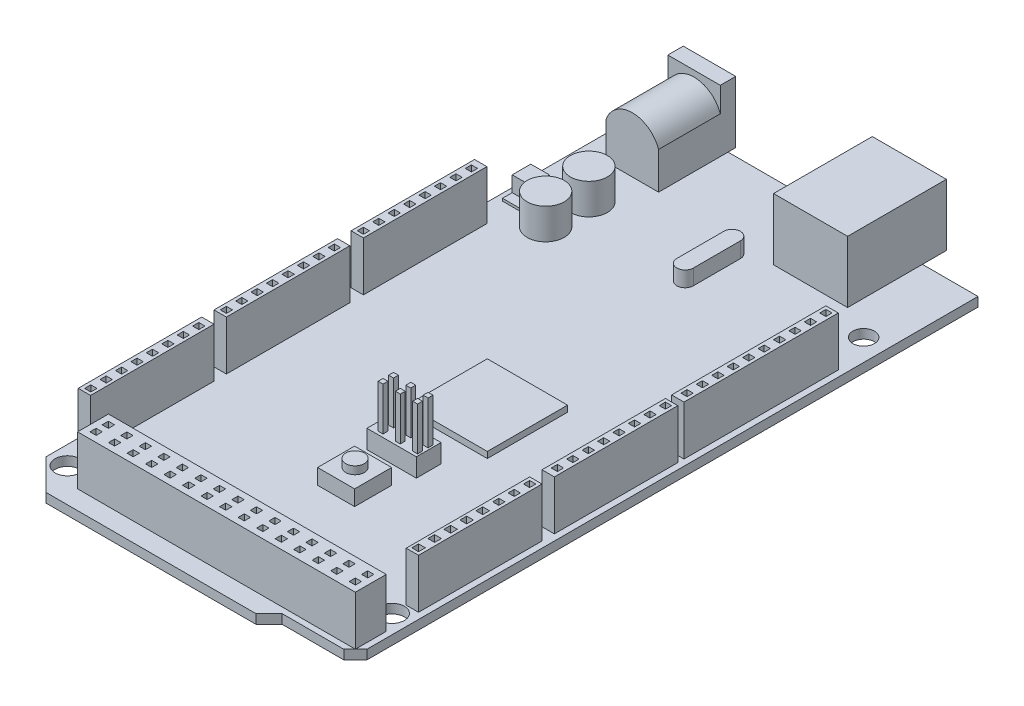
SolidWorks part; units mm, degrees
ref_plane "Front Plane" through (0, 0, 0) normal (0, 0, 1) x (1, 0, 0)
ref_plane "Top Plane" through (0, 0, 0) normal (0, 1, 0) x (1, 0, 0)
ref_plane "Right Plane" through (0, 0, 0) normal (1, 0, 0) x (0, 0, -1)
sketch "Sketch1" plane through (0, 0, 0) normal (0, 1, 0) x (1, 0, 0)
  line L0 (0, 0) -> (34, 0)
  line L1 (34, 0) -> (36.1213, 2.1213)
  line L2 (36.1213, 2.1213) -> (46.1213, 2.1213)
  line L3 (46.1213, 2.1213) -> (48, 4)
  line L4 (48, 4) -> (48, 103)
  line L5 (48, 103) -> (-5, 103)
  line L6 (-5, 103) -> (-5, 5)
  line L7 (-5, 5) -> (0, 0)
  dimension "D1" = 34
  dimension "D2" = 45
  dimension "D3" = 10
  dimension "D4" = 45
  dimension "D5" = 99
  dimension "D6" = 53
  dimension "D7" = 98
  dimension "D8" = 45
extrude "Boss-Extrude3" add sketch "Sketch1" along normal blind 1.5
sketch "Sketch4" plane through (0, 1.5, 0) normal (0, 1, 0) x (1, 0, 0)
  line L0 (46.1213, 2.1213) -> (48, 4) construction
  line L1 (47.0607, 3.0607) -> (2.0607, 3.0607)
  line L2 (47.0607, 3.0607) -> (47.0607, 8.0607)
  line L3 (47.0607, 8.0607) -> (2.0607, 8.0607)
  line L4 (2.0607, 3.0607) -> (2.0607, 8.0607)
  dimension "D1" = 45
  dimension "D2" = 5
extrude "Boss-Extrude5" add sketch "Sketch4" along normal blind 8
sketch "Sketch7" plane through (0, 9.5, 0) normal (0, 1, 0) x (1, 0, 0)
  line L0 (47.0607, 3.0607) -> (47.0607, 8.0607) construction
  line L1 (45.0607, 7.0607) -> (46.0607, 7.0607)
  line L2 (45.0607, 7.0607) -> (45.0607, 6.0607)
  line L3 (45.0607, 6.0607) -> (46.0607, 6.0607)
  line L4 (46.0607, 7.0607) -> (46.0607, 6.0607)
  line L5 (45.0607, 5.0607) -> (46.0607, 5.0607)
  line L6 (45.0607, 5.0607) -> (45.0607, 4.0607)
  line L7 (45.0607, 4.0607) -> (46.0607, 4.0607)
  line L8 (46.0607, 5.0607) -> (46.0607, 4.0607)
  line L9 (43.0607, 4.0607) -> (42.0607, 4.0607)
  line L10 (43.0607, 4.0607) -> (43.0607, 5.0607)
  line L11 (43.0607, 5.0607) -> (42.0607, 5.0607)
  line L12 (42.0607, 4.0607) -> (42.0607, 5.0607)
  line L13 (43.0607, 6.0407) -> (42.0607, 6.0407)
  line L14 (43.0607, 6.0407) -> (43.0607, 7.0407)
  line L15 (43.0607, 7.0407) -> (42.0607, 7.0407)
  line L16 (42.0607, 6.0407) -> (42.0607, 7.0407)
  line L17 (40.0607, 7.0407) -> (39.0607, 7.0407)
  line L18 (40.0607, 7.0407) -> (40.0607, 6.0407)
  line L19 (40.0607, 6.0407) -> (39.0607, 6.0407)
  line L20 (39.0607, 7.0407) -> (39.0607, 6.0407)
  line L21 (39.0607, 5.0607) -> (40.0607, 5.0607)
  line L22 (39.0607, 5.0607) -> (39.0607, 4.0607)
  line L23 (39.0607, 4.0607) -> (40.0607, 4.0607)
  line L24 (40.0607, 5.0607) -> (40.0607, 4.0607)
  line L25 (37.0607, 4.0607) -> (36.0607, 4.0607)
  line L26 (37.0607, 4.0607) -> (37.0607, 5.0607)
  line L27 (37.0607, 5.0607) -> (36.0607, 5.0607)
  line L28 (36.0607, 4.0607) -> (36.0607, 5.0607)
  line L29 (36.0607, 6.0407) -> (37.0607, 6.0407)
  line L30 (36.0607, 6.0407) -> (36.0607, 7.0407)
  line L31 (36.0607, 7.0407) -> (37.0607, 7.0407)
  line L32 (37.0607, 6.0407) -> (37.0607, 7.0407)
  line L33 (34.0607, 7.0407) -> (33.0607, 7.0407)
  line L34 (34.0607, 7.0407) -> (34.0607, 6.0407)
  line L35 (34.0607, 6.0407) -> (33.0607, 6.0407)
  line L36 (33.0607, 7.0407) -> (33.0607, 6.0407)
  line L37 (33.0607, 5.0607) -> (34.0607, 5.0607)
  line L38 (33.0607, 5.0607) -> (33.0607, 4.0607)
  line L39 (33.0607, 4.0607) -> (34.0607, 4.0607)
  line L40 (34.0607, 5.0607) -> (34.0607, 4.0607)
  line L41 (31.0607, 4.0607) -> (30.0607, 4.0607)
  line L42 (31.0607, 4.0607) -> (31.0607, 5.0607)
  line L43 (31.0607, 5.0607) -> (30.0607, 5.0607)
  line L44 (30.0607, 4.0607) -> (30.0607, 5.0607)
  line L45 (30.0607, 6.0407) -> (31.0607, 6.0407)
  line L46 (30.0607, 6.0407) -> (30.0607, 7.0407)
  line L47 (30.0607, 7.0407) -> (31.0607, 7.0407)
  line L48 (31.0607, 6.0407) -> (31.0607, 7.0407)
  line L49 (28.0607, 7.0407) -> (27.0607, 7.0407)
  line L50 (28.0607, 7.0407) -> (28.0607, 6.0407)
  line L51 (28.0607, 6.0407) -> (27.0607, 6.0407)
  line L52 (27.0607, 7.0407) -> (27.0607, 6.0407)
  line L57 (28.0607, 4.0607) -> (27.0607, 4.0607)
  line L58 (28.0607, 4.0607) -> (28.0607, 5.0607)
  line L59 (28.0607, 5.0607) -> (27.0607, 5.0607)
  line L60 (27.0607, 4.0607) -> (27.0607, 5.0607)
  line L61 (25.0607, 6.0407) -> (24.0607, 6.0407)
  line L62 (25.0607, 6.0407) -> (25.0607, 7.0407)
  line L63 (25.0607, 7.0407) -> (24.0607, 7.0407)
  line L64 (24.0607, 6.0407) -> (24.0607, 7.0407)
  line L65 (22.0607, 6.0407) -> (21.0607, 6.0407)
  line L66 (22.0607, 6.0407) -> (22.0607, 7.0407)
  line L67 (22.0607, 7.0407) -> (21.0607, 7.0407)
  line L68 (21.0607, 6.0407) -> (21.0607, 7.0407)
  line L69 (24.0607, 5.0607) -> (25.0607, 5.0607)
  line L70 (24.0607, 5.0607) -> (24.0607, 4.0607)
  line L71 (24.0607, 4.0607) -> (25.0607, 4.0607)
  line L72 (25.0607, 5.0607) -> (25.0607, 4.0607)
  line L77 (18.0607, 6.0407) -> (19.0607, 6.0407)
  line L78 (18.0607, 6.0407) -> (18.0607, 7.0407)
  line L79 (18.0607, 7.0407) -> (19.0607, 7.0407)
  line L80 (19.0607, 6.0407) -> (19.0607, 7.0407)
  line L81 (16.0607, 7.0407) -> (15.0607, 7.0407)
  line L82 (16.0607, 7.0407) -> (16.0607, 6.0407)
  line L83 (16.0607, 6.0407) -> (15.0607, 6.0407)
  line L84 (15.0607, 7.0407) -> (15.0607, 6.0407)
  line L85 (21.0607, 5.0607) -> (22.0607, 5.0607)
  line L86 (21.0607, 5.0607) -> (21.0607, 4.0607)
  line L87 (21.0607, 4.0607) -> (22.0607, 4.0607)
  line L88 (22.0607, 5.0607) -> (22.0607, 4.0607)
  line L89 (19.0607, 4.0607) -> (18.0607, 4.0607)
  line L90 (19.0607, 4.0607) -> (19.0607, 5.0607)
  line L91 (19.0607, 5.0607) -> (18.0607, 5.0607)
  line L92 (18.0607, 4.0607) -> (18.0607, 5.0607)
  line L93 (13.0607, 7.0407) -> (12.0607, 7.0407)
  line L94 (13.0607, 7.0407) -> (13.0607, 6.0407)
  line L95 (13.0607, 6.0407) -> (12.0607, 6.0407)
  line L96 (12.0607, 7.0407) -> (12.0607, 6.0407)
  line L97 (10.0607, 6.0407) -> (9.0607, 6.0407)
  line L98 (10.0607, 6.0407) -> (10.0607, 7.0407)
  line L99 (10.0607, 7.0407) -> (9.0607, 7.0407)
  line L100 (9.0607, 6.0407) -> (9.0607, 7.0407)
  line L105 (16.0607, 4.0607) -> (15.0607, 4.0607)
  line L106 (16.0607, 4.0607) -> (16.0607, 5.0607)
  line L107 (16.0607, 5.0607) -> (15.0607, 5.0607)
  line L108 (15.0607, 4.0607) -> (15.0607, 5.0607)
  line L109 (2.0607, 3.0607) -> (47.0607, 3.0607) construction
  line L110 (7.0607, 7.0407) -> (6.0607, 7.0407)
  line L111 (7.0607, 7.0407) -> (7.0607, 6.0407)
  line L112 (7.0607, 6.0407) -> (6.0607, 6.0407)
  line L113 (6.0607, 7.0407) -> (6.0607, 6.0407)
  line L114 (4.0607, 7.0407) -> (3.0607, 7.0407)
  line L115 (4.0607, 7.0407) -> (4.0607, 6.0407)
  line L116 (4.0607, 6.0407) -> (3.0607, 6.0407)
  line L121 (13.0607, 4.0607) -> (12.0607, 4.0607)
  line L122 (13.0607, 4.0607) -> (13.0607, 5.0607)
  line L123 (13.0607, 5.0607) -> (12.0607, 5.0607)
  line L124 (12.0607, 4.0607) -> (12.0607, 5.0607)
  line L125 (3.0607, 7.0407) -> (3.0607, 6.0407)
  line L137 (10.0607, 4.0607) -> (9.0607, 4.0607)
  line L138 (10.0607, 4.0607) -> (10.0607, 5.0607)
  line L139 (10.0607, 5.0607) -> (9.0607, 5.0607)
  line L140 (9.0607, 4.0607) -> (9.0607, 5.0607)
  line L153 (7.0607, 4.0607) -> (6.0607, 4.0607)
  line L154 (7.0607, 4.0607) -> (7.0607, 5.0607)
  line L155 (7.0607, 5.0607) -> (6.0607, 5.0607)
  line L156 (6.0607, 4.0607) -> (6.0607, 5.0607)
  line L169 (4.0607, 4.0607) -> (3.0607, 4.0607)
  line L170 (4.0607, 4.0607) -> (4.0607, 5.0607)
  line L171 (4.0607, 5.0607) -> (3.0607, 5.0607)
  line L172 (3.0607, 4.0607) -> (3.0607, 5.0607)
  line L182 (47.0607, 8.0607) -> (2.0607, 8.0607) construction
  dimension "D1" = 1
  dimension "D2" = 1
  dimension "D3" = 1
  dimension "D4" = 1
  dimension "D5" = 1
  dimension "D6" = 1
  dimension "D7" = 2
  dimension "D8" = 2
  dimension "D9" = 2
  dimension "D10" = 2
  dimension "D11" = 2
  dimension "D12" = 2
  dimension "D13" = 2
  dimension "D14" = 2
  dimension "D15" = 2
  dimension "D16" = 2
  dimension "D17" = 2
  dimension "D18" = 2
  dimension "D19" = 2
  dimension "D20" = 1
  dimension "D21" = 2
  dimension "D22" = 2
  dimension "D23" = 1
  dimension "D24" = 1
  dimension "D25" = 2
  dimension "D26" = 1
  dimension "D27" = 1
  dimension "D28" = 1
  dimension "D29" = 1
  dimension "D30" = 2
  dimension "D31" = 1
  dimension "D32" = 1
  dimension "D33" = 2
  dimension "D34" = 1
  dimension "D35" = 1
  dimension "D36" = 2
  dimension "D37" = 1
  dimension "D39" = 1
  dimension "D41" = 1
  dimension "D43" = 1
  dimension "D45" = 1
  dimension "D46" = 2
  dimension "D47" = 2
  dimension "D48" = 2
  dimension "D49" = 2
  dimension "D50" = 2
  dimension "D51" = 2
  dimension "D52" = 2
  dimension "D53" = 2
  dimension "D54" = 2
extrude "Cut-Extrude1" cut sketch "Sketch7" against normal up to surface (8 mm away) up to face at (26.7343, 1.5, -18.8112)
sketch "Sketch8" plane through (0, 1.5, 0) normal (0, 1, 0) x (1, 0, 0)
  line L0 (48, 4) -> (48, 103) construction
  line L1 (21, 29) -> (27, 29)
  line L2 (21, 29) -> (21, 23)
  line L3 (21, 23) -> (27, 23)
  line L4 (27, 29) -> (27, 23)
  line L5 (0, 0) -> (34, 0) construction
  dimension "D1" = 21
  dimension "D2" = 23
  dimension "D3" = 6
  dimension "D4" = 6
extrude "Boss-Extrude7" add sketch "Sketch8" along normal blind 2.5
sketch "Sketch10" plane through (0, 4, 0) normal (0, 1, 0) x (1, 0, 0)
  line L0 (21, 29) -> (21, 23) construction
  circle A0 centre (24, 26.0733) radius 1.5
  dimension "D1" = 3
  dimension "D2" = 3
extrude "Boss-Extrude8" add sketch "Sketch10" along normal blind 1.25
sketch "Sketch11" plane through (0, 1.5, 0) normal (0, 1, 0) x (1, 0, 0)
  line L0 (27, 29) -> (21, 29) construction
  line L1 (20, 36) -> (28, 36)
  line L2 (20, 36) -> (20, 32)
  line L3 (20, 32) -> (28, 32)
  line L4 (28, 36) -> (28, 32)
  line L5 (48, 4) -> (48, 103) construction
  dimension "D1" = 3
  dimension "D2" = 8
  dimension "D3" = 4
  dimension "D4" = 20
extrude "Boss-Extrude9" add sketch "Sketch11" along normal blind 3
sketch "Sketch12" plane through (0, 4.5, 0) normal (0, 1, 0) x (1, 0, 0)
  line L0 (28, 32) -> (28, 36) construction
  line L1 (26.9, 35) -> (27.7, 35)
  line L2 (26.9, 35) -> (26.9, 34.2)
  line L3 (26.9, 34.2) -> (27.7, 34.2)
  line L4 (27.7, 35) -> (27.7, 34.2)
  line L5 (24.9, 34.2) -> (24.1, 34.2)
  line L6 (24.9, 34.2) -> (24.9, 35)
  line L7 (24.9, 35) -> (24.1, 35)
  line L8 (24.1, 34.2) -> (24.1, 35)
  line L9 (21.3, 35) -> (22.1, 35)
  line L10 (21.3, 35) -> (21.3, 34.2)
  line L11 (21.3, 34.2) -> (22.1, 34.2)
  line L12 (22.1, 35) -> (22.1, 34.2)
  line L13 (21.3, 33.3) -> (22.1, 33.3)
  line L14 (21.3, 33.3) -> (21.3, 32.5)
  line L15 (21.3, 32.5) -> (22.1, 32.5)
  line L16 (22.1, 33.3) -> (22.1, 32.5)
  line L17 (24.1, 33.3) -> (24.9, 33.3)
  line L18 (24.1, 33.3) -> (24.1, 32.5)
  line L19 (24.1, 32.5) -> (24.9, 32.5)
  line L20 (24.9, 33.3) -> (24.9, 32.5)
  line L21 (26.9, 33.3) -> (27.7, 33.3)
  line L22 (26.9, 33.3) -> (26.9, 32.5)
  line L23 (26.9, 32.5) -> (27.7, 32.5)
  line L24 (27.7, 33.3) -> (27.7, 32.5)
  line L25 (28, 32) -> (28, 36) construction
  line L26 (28, 36) -> (20, 36) construction
  line L27 (20, 32) -> (28, 32) construction
  dimension "D1" = 0.8
  dimension "D2" = 0.3
  dimension "D3" = 0.3
  dimension "D4" = 1
  dimension "D5" = 0.5
  dimension "D6" = 2
  dimension "D7" = 2
  dimension "D8" = 2
  dimension "D9" = 2
extrude "Boss-Extrude10" add sketch "Sketch12" along normal blind 7
sketch "Sketch13" plane through (0, 1.5, 0) normal (0, 1, 0) x (1, 0, 0)
  line L0 (28, 36) -> (20, 36) construction
  line L1 (18, 53.5) -> (31, 53.5)
  line L2 (18, 53.5) -> (18, 40.5)
  line L3 (18, 40.5) -> (31, 40.5)
  line L4 (31, 53.5) -> (31, 40.5)
  line L5 (48, 4) -> (48, 103) construction
  dimension "D1" = 4.5
  dimension "D2" = 17
  dimension "D3" = 13
  dimension "D4" = 13
extrude "Boss-Extrude11" add sketch "Sketch13" along normal blind 1
sketch "Sketch14" plane through (0, 1.5, 0) normal (0, 1, 0) x (1, 0, 0)
  line L0 (48, 4) -> (48, 103) construction
  line L1 (27, 90.8728) -> (39, 90.8728)
  line L2 (27, 90.8728) -> (27, 106.8728)
  line L3 (27, 106.8728) -> (39, 106.8728)
  line L4 (39, 90.8728) -> (39, 106.8728)
  dimension "D1" = 9
  dimension "D2" = 12
  dimension "D3" = 16
extrude "Boss-Extrude12" add sketch "Sketch14" along normal blind 10
sketch "Sketch15" plane through (0, 0, -106.8728) normal (0, 0, -1) x (-1, 0, 0)
  line L0 (-37.5042, 2.8745) -> (-37.5042, 7.7767)
  line L1 (-37.5042, 7.7767) -> (-35.7809, 9.5)
  line L2 (-47.0607, 9.5) -> (-2.0607, 9.5) construction
  line L3 (-35.7809, 9.5) -> (-30.2715, 9.5)
  line L4 (-30.2715, 9.5) -> (-28.5482, 7.7767)
  line L5 (-28.5482, 7.7767) -> (-28.5482, 2.8745)
  line L6 (-28.5482, 2.8745) -> (-37.5042, 2.8745)
extrude "Cut-Extrude2" cut sketch "Sketch15" against normal blind 13
sketch "Sketch16" plane through (0, 0, -93.8728) normal (0, 0, -1) x (-1, 0, 0)
  line L0 (-37.5042, 7.7767) -> (-37.5042, 2.8745) construction
  line L1 (-35.8042, 7.78) -> (-30.2482, 7.78)
  line L2 (-35.8042, 7.78) -> (-35.8042, 4.3976)
  line L3 (-35.8042, 4.3976) -> (-30.2482, 4.3976)
  line L4 (-30.2482, 7.78) -> (-30.2482, 4.3976)
  line L5 (-28.5482, 2.8745) -> (-28.5482, 7.7767) construction
  dimension "D1" = 1.7
  dimension "D2" = 1.7
extrude "Boss-Extrude13" add sketch "Sketch16" along normal up to surface (13 mm away) up to face at (33.0262, 6.7171, -106.8728)
sketch "Sketch17" plane through (0, 0, -103) normal (0, 0, -1) x (-1, 0, 0)
  line L0 (-27, 1.5) -> (5, 1.5) construction
  line L1 (1, 1.5) -> (-7.5, 1.5)
  line L2 (1, 1.5) -> (1, 11.5)
  line L3 (1, 11.5) -> (-7.5, 11.5)
  line L4 (-7.5, 1.5) -> (-7.5, 11.5)
  dimension "D1" = 4
  dimension "D2" = 10
  dimension "D3" = 8.5
extrude "Boss-Extrude14" add sketch "Sketch17" along normal mid plane 2.5
sketch "Sketch18" plane through (0, 0, -101.75) normal (0, 0, 1) x (1, 0, 0)
  line L0 (-1, 7.5) -> (-1, 1.5)
  line L1 (-1, 1.5) -> (-1, 11.5) construction
  line L2 (-1, 1.5) -> (7.5, 1.5)
  line L3 (7.5, 1.5) -> (-1, 1.5) construction
  line L4 (7.5, 1.5) -> (7.5, 7.5)
  line L5 (7.5, 11.5) -> (7.5, 1.5) construction
  arc A0 (-1, 7.5) -> (7.5, 7.5) centre (3.25, 6.021) cw
  dimension "D3" = 4.5
  dimension "D1" = 6
  dimension "D2" = 6
extrude "Boss-Extrude15" add sketch "Sketch18" along normal blind 10
sketch "Sketch19" plane through (0, 0, -104.25) normal (0, 0, -1) x (-1, 0, 0)
  line L0 (1, 1.5) -> (1, 11.5) construction
  line L1 (1, 11.5) -> (-7.5, 11.5) construction
  circle A0 centre (-3, 6.5) radius 3
  dimension "D1" = 6
  dimension "D2" = 4
  dimension "D3" = 5
extrude "Cut-Extrude6" cut sketch "Sketch19" against normal blind 10
sketch "Sketch20" plane through (0, 0, -94.25) normal (0, 0, -1) x (-1, 0, 0)
  circle A0 centre (-3, 6.5) radius 0.5
  circle A1 centre (-3, 6.5) radius 3 construction
  dimension "D1" = 1
  dimension "D2" = 0
extrude "Boss-Extrude16" add sketch "Sketch20" along normal blind 8
dome "Dome1" faces to dome 1 distance 1 reverse direction no elliptical dome no face at (2.5, 6.5, -102.25) parameters "D1"=1
sketch "Sketch21" plane through (0, 1.5, 0) normal (0, 1, 0) x (1, 0, 0)
  line L0 (-1, 91.75) -> (7.5, 91.75) construction
  circle A0 centre (3.2048, 84.75) radius 3
  circle A1 centre (3.2048, 77.75) radius 3
  point P7 (3.25, 91.75)
  dimension "D1" = 6
  dimension "D2" = 6
  dimension "D3" = 7
  dimension "D4" = 7
extrude "Boss-Extrude17" add sketch "Sketch21" along normal blind 5
sketch "Sketch23" plane through (0, 1.5, 0) normal (0, 1, 0) x (1, 0, 0)
  line L1 (-3.8978, 84.0356) -> (-0.8721, 84.0356)
  line L2 (-3.8978, 84.0356) -> (-3.8978, 77.8497)
  line L3 (-3.8978, 77.8497) -> (-0.8721, 77.8497)
  line L4 (-0.8721, 84.0356) -> (-0.8721, 77.8497)
extrude "Boss-Extrude18" add sketch "Sketch23" along normal blind 0.4
sketch "Sketch24" plane through (0, 1.9, 0) normal (0, 1, 0) x (1, 0, 0)
  line L0 (-3.8978, 84.0356) -> (-3.8978, 77.8497) construction
  line L1 (-3.8978, 82.4355) -> (-0.8721, 82.4355)
  line L2 (-3.8978, 82.4355) -> (-3.8978, 79.4247)
  line L3 (-3.8978, 79.4247) -> (-0.8721, 79.4247)
  line L4 (-0.8721, 82.4355) -> (-0.8721, 79.4247)
  line L5 (-0.8721, 77.8497) -> (-0.8721, 84.0356) construction
extrude "Boss-Extrude19" add sketch "Sketch24" along normal blind 2.5
sketch "Sketch25" plane through (0, 1.5, 0) normal (0, 1, 0) x (1, 0, 0)
  line L0 (20.7718, 89.0501) -> (20.7718, 81.4302)
  line L2 (23.4528, 81.4302) -> (23.4528, 89.0501)
  arc A0 (20.7718, 89.0501) -> (23.4528, 89.0501) centre (22.1123, 89.0501) cw
  arc A1 (20.7718, 81.4302) -> (23.4528, 81.4302) centre (22.1123, 81.4302) ccw
extrude "Boss-Extrude20" add sketch "Sketch25" along normal blind 2.5
sketch "Sketch26" plane through (0, 1.5, 0) normal (0, 1, 0) x (1, 0, 0)
  line L0 (-5, 103) -> (-5, 5) construction
  line L1 (-1, 103) -> (-5, 103) construction
  circle A0 centre (-2, 89) radius 2
  dimension "D1" = 4
  dimension "D2" = 3
  dimension "D3" = 14
extrude "Cut-Extrude7" cut sketch "Sketch26" against normal up to surface (1.5 mm away) up to face at (25.2803, 0, -27.4053)
sketch "Sketch27" plane through (0, 1.5, 0) normal (0, 1, 0) x (1, 0, 0)
  line L0 (-5, 103) -> (-5, 5) construction
  circle A0 centre (-2, 5.4729) radius 2
  dimension "D1" = 4
  dimension "D2" = 3
extrude "Cut-Extrude8" cut sketch "Sketch27" against normal up to surface (1.5 mm away) up to face at (-2, 0, -87)
sketch "Sketch28" plane through (0, 1.5, 0) normal (0, 1, 0) x (1, 0, 0)
  line L0 (48, 4) -> (48, 103) construction
  line L1 (47.0607, 8.0607) -> (2.0607, 8.0607) construction
  circle A0 centre (45, 11.0607) radius 2
  dimension "D1" = 4
  dimension "D2" = 3
  dimension "D3" = 3
extrude "Cut-Extrude9" cut sketch "Sketch28" against normal up to surface (1.5 mm away) up to face at (-2, 0, -3.4729)
sketch "Sketch29" plane through (0, 1.5, 0) normal (0, 1, 0) x (1, 0, 0)
  line L0 (48, 4) -> (48, 103) construction
  line L1 (47, 13.3607) -> (45, 13.3607)
  line L2 (47, 13.3607) -> (47, 33.3607)
  line L3 (47, 33.3607) -> (45, 33.3607)
  line L4 (45, 13.3607) -> (45, 33.3607)
  circle A0 centre (45, 11.0607) radius 2 construction
  dimension "D1" = 20
  dimension "D2" = 2
  dimension "D3" = 2.3
  dimension "D4" = 1
extrude "Boss-Extrude21" add sketch "Sketch29" along normal blind 8
sketch "Sketch30" plane through (0, 9.5, 0) normal (0, 1, 0) x (1, 0, 0)
  line L0 (45, 33.3607) -> (45, 13.3607) construction
  line L1 (45.5, 32.8607) -> (46.5, 32.8607)
  line L2 (45.5, 32.8607) -> (45.5, 31.8607)
  line L3 (45.5, 31.8607) -> (46.5, 31.8607)
  line L4 (46.5, 32.8607) -> (46.5, 31.8607)
  line L5 (45.5, 30.3607) -> (46.5, 30.3607)
  line L6 (45.5, 30.3607) -> (45.5, 29.3607)
  line L7 (45.5, 29.3607) -> (46.5, 29.3607)
  line L8 (46.5, 30.3607) -> (46.5, 29.3607)
  line L10 (45.5, 26.8607) -> (46.5, 26.8607)
  line L11 (45.5, 26.8607) -> (45.5, 27.8607)
  line L12 (45.5, 27.8607) -> (46.5, 27.8607)
  line L13 (45.4, 25.3607) -> (46.5, 25.3607)
  line L14 (45.4, 25.3607) -> (45.4, 24.2607)
  line L15 (45.4, 24.2607) -> (46.5, 24.2607)
  line L16 (46.5, 25.3607) -> (46.5, 24.2607)
  line L17 (45.4, 22.7607) -> (46.5, 22.7607)
  line L18 (45.4, 22.7607) -> (45.4, 21.6607)
  line L19 (45.4, 21.6607) -> (46.5, 21.6607)
  line L20 (46.5, 22.7607) -> (46.5, 21.6607)
  line L21 (45.4, 20.1607) -> (46.5, 20.1607)
  line L22 (45.4, 20.1607) -> (45.4, 19.0607)
  line L23 (45.4, 19.0607) -> (46.5, 19.0607)
  line L24 (46.5, 20.1607) -> (46.5, 19.0607)
  line L25 (45.4, 17.5607) -> (46.5, 17.5607)
  line L26 (45.4, 17.5607) -> (45.4, 16.4607)
  line L27 (45.4, 16.4607) -> (46.5, 16.4607)
  line L28 (46.5, 17.5607) -> (46.5, 16.4607)
  line L29 (45.4, 14.9607) -> (46.5, 14.9607)
  line L30 (45.4, 14.9607) -> (45.4, 13.8607)
  line L31 (45.4, 13.8607) -> (46.5, 13.8607)
  line L32 (46.5, 14.9607) -> (46.5, 13.8607)
  line L33 (47, 33.3607) -> (45, 33.3607) construction
  line L34 (45, 13.3607) -> (47, 13.3607) construction
  line L35 (46.5, 26.8607) -> (46.5, 27.8607)
  dimension "D1" = 1
  dimension "D2" = 1
  dimension "D3" = 0.5
  dimension "D4" = 0.5
  dimension "D5" = 1.5
  dimension "D6" = 1.5
  dimension "D7" = 1.5
  dimension "D8" = 1.5
  dimension "D9" = 1.1
  dimension "D10" = 0.5
  dimension "D11" = 1.5
  dimension "D12" = 1
  dimension "D13" = 1.5
  dimension "D14" = 1.5
extrude "Cut-Extrude10" cut sketch "Sketch30" against normal up to surface (8 mm away) up to face at (22.1123, 1.5, -85.2402)
sketch "Sketch32" plane through (0, 1.5, 0) normal (0, 1, 0) x (1, 0, 0)
  line L0 (47, 33.3607) -> (45, 33.3607) construction
  line L1 (47, 35.3607) -> (45, 35.3607)
  line L2 (47, 35.3607) -> (47, 55.3607)
  line L3 (47, 55.3607) -> (45, 55.3607)
  line L4 (45, 35.3607) -> (45, 55.3607)
  line L5 (48, 4) -> (48, 103) construction
  dimension "D1" = 20
  dimension "D2" = 2
  dimension "D3" = 2
  dimension "D4" = 1
extrude "Boss-Extrude22" add sketch "Sketch32" along normal blind 8
sketch "Sketch34" plane through (0, 9.5, 0) normal (0, 1, 0) x (1, 0, 0)
  line L0 (45, 55.3607) -> (45, 35.3607) construction
  line L1 (45.5, 54.8607) -> (46.5, 54.8607)
  line L2 (45.5, 54.8607) -> (45.5, 53.8607)
  line L3 (45.5, 53.8607) -> (46.5, 53.8607)
  line L4 (46.5, 54.8607) -> (46.5, 53.8607)
  line L5 (47, 55.3607) -> (45, 55.3607) construction
  dimension "D1" = 1
  dimension "D2" = 1
  dimension "D3" = 0.5
  dimension "D4" = 0.5
extrude "Cut-Extrude11" cut sketch "Sketch34" against normal up to surface (8 mm away) up to face at (46, 1.5, -23.3607)
sketch "Sketch35" plane through (0, 9.5, 0) normal (0, 1, 0) x (1, 0, 0)
  line L0 (45.9896, 51.566) -> (46, 53.8607) construction
  line L1 (45.5, 53.8607) -> (46.5, 53.8607) construction
  line L2 (46, 53.8607) -> (46, 35.3607) construction
  line L3 (45, 35.3607) -> (47, 35.3607) construction
pattern_linear "LPattern1" count 8 spacing 2.5 along (0, 0, 1) of "Cut-Extrude11"
sketch "Sketch37" plane through (0, 1.5, 0) normal (0, 1, 0) x (1, 0, 0)
  line L0 (48, 4) -> (48, 103) construction
  line L1 (47, 56.3607) -> (45, 56.3607)
  line L2 (47, 56.3607) -> (47, 81.3607)
  line L3 (47, 81.3607) -> (45, 81.3607)
  line L4 (45, 56.3607) -> (45, 81.3607)
  line L5 (47, 55.3607) -> (45, 55.3607) construction
  dimension "D1" = 25
  dimension "D2" = 2
  dimension "D3" = 1
  dimension "D4" = 1
extrude "Boss-Extrude24" add sketch "Sketch37" along normal blind 8
sketch "Sketch41" plane through (0, 9.5, 0) normal (0, 1, 0) x (1, 0, 0)
  line L0 (47, 81.3607) -> (45, 81.3607) construction
  line L1 (45.5, 80.8607) -> (46.5, 80.8607)
  line L2 (45.5, 80.8607) -> (45.5, 79.8607)
  line L3 (45.5, 79.8607) -> (46.5, 79.8607)
  line L4 (46.5, 80.8607) -> (46.5, 79.8607)
  line L5 (45, 81.3607) -> (45, 56.3607) construction
  point P4 (46, 81.3607)
  dimension "D1" = 0.5
  dimension "D2" = 0.5
  dimension "D3" = 1
  dimension "D4" = 1
extrude "Cut-Extrude13" cut sketch "Sketch41" against normal up to surface (8 mm away) up to face at (46, 1.5, -45.3607)
sketch "Sketch43" plane through (0, 9.5, 0) normal (0, 1, 0) x (1, 0, 0)
  line L0 (46, 81.3607) -> (46, 56.3607) construction
  line L1 (47, 81.3607) -> (45, 81.3607) construction
  line L2 (45, 56.3607) -> (47, 56.3607) construction
pattern_linear "LPattern3" count 10 spacing 2.5 along (0, 0, 1) of "Cut-Extrude13"
sketch "Sketch45" plane through (0, 1.5, 0) normal (0, 1, 0) x (1, 0, 0)
  line L0 (48, 4) -> (48, 103) construction
  line L1 (48, 103) -> (39, 103) construction
  circle A0 centre (44.475, 88) radius 1.75
  point P5 (43.5, 103)
  dimension "D1" = 3.5
  dimension "D2" = 3.525
  dimension "D3" = 15
extrude "Cut-Extrude14" cut sketch "Sketch45" against normal up to surface (1.5 mm away) up to face at (45, 0, -9.0607)
sketch "Sketch46" plane through (0, 1.5, 0) normal (0, 1, 0) x (1, 0, 0)
  line L0 (-5, 103) -> (-5, 5) construction
  line L1 (-2, 9.2229) -> (-4, 9.2229)
  line L2 (-2, 9.2229) -> (-2, 29.2229)
  line L3 (-2, 29.2229) -> (-4, 29.2229)
  line L4 (-4, 9.2229) -> (-4, 29.2229)
  circle A0 centre (-2, 5.4729) radius 2 construction
  dimension "D4" = 3.75
  dimension "D1" = 20
  dimension "D2" = 2
  dimension "D3" = 1
extrude "Boss-Extrude25" add sketch "Sketch46" along normal blind 8
sketch "Sketch47" plane through (0, 9.5, 0) normal (0, 1, 0) x (1, 0, 0)
  line L0 (-4, 9.2229) -> (-2, 9.2229) construction
  line L1 (-2.4665, 9.7229) -> (-3.4665, 9.7229)
  line L2 (-2.4665, 9.7229) -> (-2.4665, 10.7229)
  line L3 (-2.4665, 10.7229) -> (-3.4665, 10.7229)
  line L4 (-3.4665, 9.7229) -> (-3.4665, 10.7229)
  point P4 (-3, 9.2229)
  dimension "D1" = 0.5
  dimension "D2" = 1
  dimension "D3" = 1
extrude "Cut-Extrude15" cut sketch "Sketch47" against normal up to surface (8 mm away) up to face at (46, 1.5, -68.8607)
sketch "Sketch48" plane through (0, 9.5, 0) normal (0, 1, 0) x (1, 0, 0)
  line L0 (-3, 9.2229) -> (-3, 29.2229) construction
  line L1 (-4, 9.2229) -> (-2, 9.2229) construction
  line L2 (-2, 29.2229) -> (-4, 29.2229) construction
pattern_linear "LPattern4" count 8 spacing 2.5 along (0, 0, -1) of "Cut-Extrude15"
sketch "Sketch49" plane through (0, 1.5, 0) normal (0, 1, 0) x (1, 0, 0)
  line L0 (-5, 103) -> (-5, 5) construction
  line L1 (-2, 31.2229) -> (-4, 31.2229)
  line L2 (-2, 31.2229) -> (-2, 51.2229)
  line L3 (-2, 51.2229) -> (-4, 51.2229)
  line L4 (-4, 31.2229) -> (-4, 51.2229)
  dimension "D1" = 2
  dimension "D2" = 20
  dimension "D3" = 2
  dimension "D4" = 1
extrude "Boss-Extrude26" add sketch "Sketch49" along normal blind 8
sketch "Sketch50" plane through (0, 9.5, 0) normal (0, 1, 0) x (1, 0, 0)
  line L0 (-4, 31.2229) -> (-2, 31.2229) construction
  line L1 (-2.5, 31.7229) -> (-3.5, 31.7229)
  line L2 (-2.5, 31.7229) -> (-2.5, 32.7229)
  line L3 (-2.5, 32.7229) -> (-3.5, 32.7229)
  line L4 (-3.5, 31.7229) -> (-3.5, 32.7229)
  line L5 (-4, 51.2229) -> (-4, 31.2229) construction
  dimension "D1" = 0.5
  dimension "D2" = 1
  dimension "D3" = 1
  dimension "D4" = 0.5
extrude "Cut-Extrude16" cut sketch "Sketch50" against normal up to surface (8 mm away) up to face at (-3, 1.5, -19.2229)
sketch "Sketch51" plane through (0, 9.5, 0) normal (0, 1, 0) x (1, 0, 0)
  line L0 (-3, 31.2229) -> (-3, 51.2229) construction
  line L1 (-4, 31.2229) -> (-2, 31.2229) construction
  line L2 (-2, 51.2229) -> (-4, 51.2229) construction
pattern_linear "LPattern5" count 8 spacing 2.5 along (0, 0, -1) of "Cut-Extrude16"
sketch "Sketch52" plane through (0, 1.5, 0) normal (0, 1, 0) x (1, 0, 0)
  line L0 (-5, 103) -> (-5, 5) construction
  line L1 (-2, 53.4274) -> (-4, 53.4274)
  line L2 (-2, 53.4274) -> (-2, 73.4274)
  line L3 (-2, 73.4274) -> (-4, 73.4274)
  line L4 (-4, 53.4274) -> (-4, 73.4274)
  dimension "D1" = 2
  dimension "D2" = 1
  dimension "D3" = 20
extrude "Boss-Extrude27" add sketch "Sketch52" along normal blind 8
sketch "Sketch53" plane through (0, 9.5, 0) normal (0, 1, 0) x (1, 0, 0)
  line L0 (-4, 53.4274) -> (-2, 53.4274) construction
  line L1 (-2.5, 53.9274) -> (-3.5, 53.9274)
  line L2 (-2.5, 53.9274) -> (-2.5, 54.9274)
  line L3 (-2.5, 54.9274) -> (-3.5, 54.9274)
  line L4 (-3.5, 53.9274) -> (-3.5, 54.9274)
  line L5 (-4, 73.4274) -> (-4, 53.4274) construction
  point P4 (-3, 53.4274)
  dimension "D1" = 0.5
  dimension "D2" = 0.5
  dimension "D3" = 1
  dimension "D4" = 1
extrude "Cut-Extrude17" cut sketch "Sketch53" against normal up to surface (8 mm away) up to face at (-3, 1.5, -41.2229)
sketch "Sketch54" plane through (0, 9.5, 0) normal (0, 1, 0) x (1, 0, 0)
  line L0 (-3, 53.4274) -> (-3, 73.4274) construction
  line L1 (-4, 53.4274) -> (-2, 53.4274) construction
  line L2 (-2, 73.4274) -> (-4, 73.4274) construction
pattern_linear "LPattern6" count 8 spacing 2.5 along (0, 0, -1) of "Cut-Extrude17"
sketch "Sketch55" plane through (0, 1.5, 0) normal (0, 1, 0) x (1, 0, 0)
  text T0 "ARDUINO"
